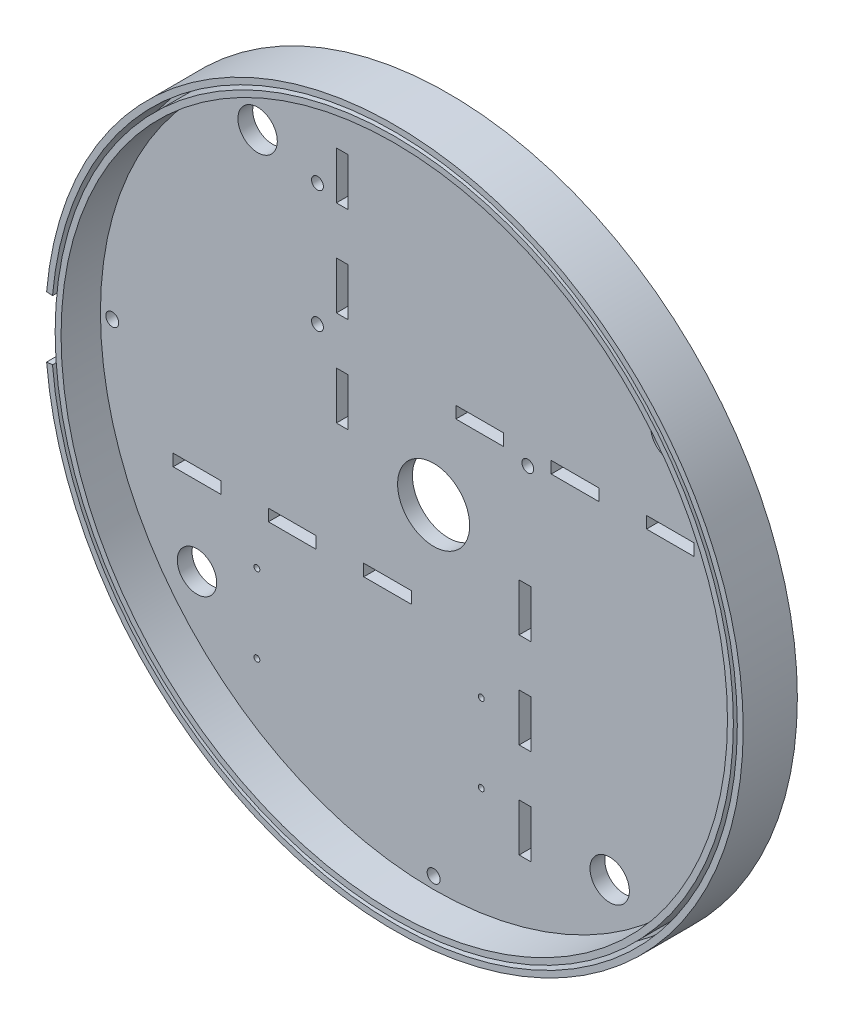
SolidWorks part; units mm, degrees
material "ABS"
ref_plane "Front Plane" through (0, 0, 0) normal (0, 0, 1) x (1, 0, 0)
ref_plane "Top Plane" through (0, 0, 0) normal (0, 1, 0) x (1, 0, 0)
ref_plane "Right Plane" through (0, 0, 0) normal (1, 0, 0) x (0, 0, -1)
sketch "Sketch1" plane through (0, 0, 0) normal (0, 0, 1) x (1, 0, 0)
  line L0 (0, 0) -> (0, -100) construction
  line L1 (-100, -100) -> (100, -100)
  line L2 (-100, -100) -> (-100, 100)
  line L3 (100, -100) -> (100, 100)
  line L4 (100, 100) -> (-100, 100)
  circle A0 centre (0, 0) radius 9.15
  point P7 (0, -100)
  dimension "D1" = 18.3
  dimension "D2" = 100
  dimension "D3" = 200
  dimension "D4" = 200
extrude "Boss-Extrude1" add sketch "Sketch1" against normal blind 3.75
sketch "Sketch2" plane through (0, 0, 0) normal (0, 0, 1) x (1, 0, 0)
  line L0 (0, 0) -> (0, 14.2) construction
  line L1 (0, 10.9) -> (0, 14.2)
  line L2 (8.825, 11.1247) -> (6.1526, 7.756)
  line L3 (-0.8481, 14.1747) -> (-0.5913, 9.8823)
  circle A0 centre (0, 0) radius 10.9 construction
  circle A1 centre (0, 0) radius 14.2
  circle A2 centre (0, 0) radius 10.9
  arc A3 (0, 12.55) -> (-0.7496, 12.5276) centre (0, 0) ccw construction
  arc A4 (0, 12.55) -> (0.7496, 12.5276) centre (0, 0) cw construction
  arc A5 (0.7496, 12.5276) -> (7.7995, 9.8321) centre (0, 0) cw construction
  arc A6 (0.8481, 14.1747) -> (8.825, 11.1247) centre (0, 0) cw
  arc A7 (0, 14.2) -> (0.8481, 14.1747) centre (0, 0) cw
  arc A8 (0, 14.2) -> (-0.8481, 14.1747) centre (0, 0) ccw
  arc A9 (0.5913, 9.8823) -> (6.1526, 7.756) centre (0, 0) cw
  arc A10 (0, 9.9) -> (0.5913, 9.8823) centre (0, 0) cw
  arc A11 (0, 9.9) -> (-0.5913, 9.8823) centre (0, 0) ccw
  dimension "D2" = 0.75
  dimension "D3" = 0.75
  dimension "D4" = 35
  dimension "D1" = 3.3
  dimension "D5" = 1.65
  dimension "D6" = 2.65
extrude "Cut-Extrude4" [suppressed] cut sketch "Sketch2" against normal mid plane 1.65 from offset 1.5 contours L2 A9 A10 A11 L3 A8 A7 A6 offset against normal yes
sketch "Sketch4" [suppressed] plane through (0, 0, -4.325) normal (0, 0, 1) x (1, 0, 0)
  line L0 (4.1191, 9.2766) -> (7.6444, 13.4263)
  line L1 (8.5363, 5.4912) -> (12.0972, 9.6104)
  arc A0 (6.6047, 7.7071) -> (8.5363, 5.4912) centre (0, 0) cw
  arc A1 (6.6047, 7.7071) -> (4.1191, 9.2766) centre (0, 0) ccw
  arc A2 (10.0535, 11.7316) -> (7.6444, 13.4263) centre (0, 0) ccw
  arc A3 (10.0535, 11.7316) -> (12.0972, 9.6104) centre (0, 0) cw
  dimension "D1" = 1.95
  dimension "D2" = 1.95
  dimension "D3" = 1.95
  dimension "D4" = 1.95
extrude "Cut-Extrude5" [suppressed] cut sketch "Sketch4" along normal through all
pattern_circular "CirPattern1" [suppressed] count 4 over 360 of bodies 108
sketch "Sketch5" plane through (0, 0, 0) normal (0, 0, 1) x (1, 0, 0)
  line L0 (0, 0) -> (15, 0)
  line L1 (15, 0) -> (47, 0)
  line L2 (47, 0) -> (15.5, 0)
  line L3 (15.5, 0) -> (5.65, 0)
  line L4 (5.65, 0) -> (5.65, 21.7)
  line L5 (5.65, 21.7) -> (17.75, 21.7)
  line L6 (5.65, 21.7) -> (5.65, 24.7)
  line L7 (17.75, 21.7) -> (17.75, 24.7)
  line L8 (5.65, 24.7) -> (17.75, 24.7)
  line L9 (17.75, 21.7) -> (29.85, 21.7)
  line L10 (29.85, 21.7) -> (29.85, 24.7)
  line L11 (29.85, 21.7) -> (41.95, 21.7)
  line L12 (29.85, 24.7) -> (41.95, 24.7)
  line L13 (41.95, 21.7) -> (41.95, 24.7)
  line L14 (41.95, 21.7) -> (54.05, 21.7)
  line L15 (54.05, 21.7) -> (66.15, 21.7)
  line L16 (54.05, 21.7) -> (54.05, 24.7)
  line L17 (66.15, 21.7) -> (66.15, 24.7)
  line L18 (54.05, 24.7) -> (66.15, 24.7)
  line L19 (60.1, 24.7) -> (60.1, 44.7) construction
  circle A0 centre (60.1, 44.7) radius 5
  point P22 (60.1, 24.7)
  dimension "D15" = 10
  dimension "D1" = 15
  dimension "D2" = 32
  dimension "D3" = 31.5
  dimension "D4" = 9.85
  dimension "D5" = 21.7
  dimension "D6" = 12.1
  dimension "D7" = 3
  dimension "D8" = 12.1
  dimension "D9" = 12.1
  dimension "D10" = 12.1
  dimension "D11" = 12.1
  dimension "D12" = 3
  dimension "D13" = 3
  dimension "D14" = 20
extrude "Cut-Extrude6" cut sketch "Sketch5" against normal blind 10 contours L11 L13 L12 L10 | L18 L16 L15 L17 | L5 L6 L8 L7 | A0 region at (60.1, 23.2, 0) region at (35.9, 23.2, 0)
pattern_circular "CirPattern2" count 4 over 360 about axis through (0, 0, -3.75) along (0, 0, 1) of "Cut-Extrude6"
sketch "Sketch6" plane through (0, 0, 0) normal (0, 0, 1) x (1, 0, 0)
  line L1 (100, 100) -> (-100, 100)
  line L2 (100, 100) -> (100, -100)
  line L3 (100, -100) -> (-100, -100)
  line L4 (-100, 100) -> (-100, -100)
  line L5 (100, 100) -> (-100, -100) construction
  line L6 (100, -100) -> (-100, 100) construction
  circle A0 centre (0, 0) radius 70.611 construction
  circle A1 centre (0, 0) radius 88.611
extrude "Cut-Extrude10" cut sketch "Sketch6" against normal through all contours L1 L4 L3 L2 A1 region at (97.1716, 0, 0)
sketch "Sketch7" plane through (0, 0, 0) normal (0, 0, 1) x (1, 0, 0)
  line L0 (-80.611, 0) -> (0, 0) construction
  line L1 (-88.2738, 7.723) -> (-86.7795, 7.5922)
  line L2 (-88.2738, -7.723) -> (-86.7795, -7.5922)
  circle A0 centre (0, 0) radius 88.611 construction
  arc A1 (-88.2738, -7.723) -> (-88.2738, 7.723) centre (0, 0) cw construction
  arc A2 (-88.2738, 7.723) -> (-88.2738, -7.723) centre (0, 0) cw
  arc A3 (-86.7795, 7.5922) -> (-86.7795, -7.5922) centre (0, 0) cw
  circle A4 centre (0, 0) radius 86.111
  circle A5 centre (0, 0) radius 84.611
  circle A6 centre (0, 0) radius 88.611 construction
  dimension "D1" = 1.5
  dimension "D2" = 2.5
  dimension "D3" = 1.5
extrude "Boss-Extrude2" add sketch "Sketch7" along normal blind 10
sketch "Sketch8" plane through (0, 0, -3.75) normal (0, 0, -1) x (-1, 0, 0)
  line L0 (0, 0) -> (-88.611, 0) construction
  line L1 (0, 0) -> (-83.2671, -30.3067) construction
  circle A0 centre (0, 0) radius 88.611 construction
  dimension "D1" = 20
ref_plane "Plane1" through (83.2671, 0, 0) normal (1, 0, 0) x (0, 0, -1)
sketch "Sketch9" plane through (83.2671, 0, 0) normal (1, 0, 0) x (0, 0, -1)
  line L0 (3.75, -30.3067) -> (0, -30.3067) construction
  circle A0 centre (1.875, -30.3067) radius 0.75
  dimension "D1" = 3.75
  dimension "D2" = 1.5
sketch "Sketch10" plane through (0, 0, -3.75) normal (0, 0, -1) x (-1, 0, 0)
  point P0 (29.5, 56)
  point P1 (29.5, 25)
  point P2 (-23.9, 20.5)
  point P3 (-23.9, 70.5)
  point P4 (44.8862, -36.3499)
  point P5 (44.8862, -56.2286)
  point P7 (-12.0925, -56.2286)
  point P9 (-12.0925, -36.3499)
  dimension "D1" = 31
  dimension "D2" = 50
  dimension "D3" = 53.4
  dimension "D4" = 19.8787
  dimension "D5" = 56.9787
  dimension "D6" = 19.8787
  dimension "D7" = 25
  dimension "D8" = 29.5
  dimension "D9" = 20.5
sketch "Sketch11" plane through (0, 0, -3.75) normal (0, 0, -1) x (-1, 0, 0)
  line L0 (29.5, 56) -> (29.5, 25) construction
  line L1 (-23.9, 70.5) -> (-23.9, 20.5) construction
  line L2 (-26.4, 70.5) -> (-26.4, 20.5)
  line L3 (-21.4, 70.5) -> (-21.4, 20.5)
  line L10 (27, 56) -> (27, 25)
  line L11 (32, 56) -> (32, 25)
  circle A0 centre (29.5, 25) radius 1.5
  circle A1 centre (29.5, 56) radius 1.5
  circle A2 centre (-23.9, 70.5) radius 1.5
  circle A3 centre (-23.9, 20.5) radius 1.5
  arc A4 (27, 56) -> (32, 56) centre (29.5, 56) cw
  arc A5 (27, 25) -> (32, 25) centre (29.5, 25) ccw
  arc A6 (-26.4, 70.5) -> (-21.4, 70.5) centre (-23.9, 70.5) cw
  arc A7 (-26.4, 20.5) -> (-21.4, 20.5) centre (-23.9, 20.5) ccw
  dimension "D13" = 3
  dimension "D14" = 3
  dimension "D15" = 3
  dimension "D16" = 3
  dimension "D2" = 2.5
  dimension "D3" = 2.5
  dimension "D7" = 2.5
  dimension "D8" = 2.5
extrude "Boss-Extrude3" add sketch "Sketch11" along normal blind 5
sketch "Sketch13" plane through (0, 0, -3.75) normal (0, 0, -1) x (-1, 0, 0)
  circle A0 centre (29.5, 56) radius 1.5
  circle A1 centre (29.5, 25) radius 1.5
  circle A2 centre (-23.9, 20.5) radius 1.5
  circle A3 centre (-23.9, 70.5) radius 1.5
extrude "Cut-Extrude11" cut sketch "Sketch13" against normal through all
sketch "Sketch14" plane through (0, 0, -3.75) normal (0, 0, -1) x (-1, 0, 0)
  line L0 (44.8862, -36.3499) -> (44.8862, -56.2286)
  line L1 (-12.0925, -36.3499) -> (-12.0925, -56.2286)
  line L2 (-9.5925, -36.3499) -> (-9.5925, -56.2286)
  line L3 (-14.5925, -36.3499) -> (-14.5925, -56.2286)
  line L4 (42.3862, -36.3499) -> (42.3862, -56.2286)
  line L5 (47.3862, -36.3499) -> (47.3862, -56.2286)
  arc A0 (-9.5925, -36.3499) -> (-14.5925, -36.3499) centre (-12.0925, -36.3499) ccw
  arc A1 (-9.5925, -56.2286) -> (-14.5925, -56.2286) centre (-12.0925, -56.2286) cw
  arc A2 (42.3862, -36.3499) -> (47.3862, -36.3499) centre (44.8862, -36.3499) cw
  arc A3 (42.3862, -56.2286) -> (47.3862, -56.2286) centre (44.8862, -56.2286) ccw
  circle A4 centre (44.8862, -36.3499) radius 0.75
  circle A6 centre (-12.0925, -56.2286) radius 0.75
  circle A7 centre (-12.0925, -36.3499) radius 0.75
  circle A8 centre (44.8862, -56.2286) radius 0.75
  dimension "D5" = 1.5
  dimension "D6" = 1.5
  dimension "D7" = 1.5
  dimension "D8" = 1.5
  dimension "D1" = 2.5
  dimension "D2" = 2.5
  dimension "D3" = 2.5
  dimension "D4" = 2.5
extrude "Boss-Extrude4" add sketch "Sketch14" along normal blind 3 contours L4 A3 L5 A2 A8 A4 | A1 L2 A0 L3 A7 A6 region at (9.8462, -46.2892, -3.75) region at (-44.8862, -34.1037, -3.75)
extrude "Cut-Extrude12" cut sketch "Sketch14<3>" against normal through all contours A4 | A8 | A6 | A7
sketch "Sketch14<3>" plane through (0, 0, -3.75) normal (0, 0, -1) x (-1, 0, 0) same geometry as "Sketch14"
sketch "Sketch15" plane through (0, 0, 0) normal (0, 0, 1) x (1, 0, 0)
  line L0 (0, 0) -> (-86.111, 0) construction
  line L1 (-86.111, 0) -> (-81.611, 0)
  circle A0 centre (0, 0) radius 86.111 construction
  dimension "D1" = 4.5
hole_wizard "Tap Drill for M4x0.7 Tap1" positions "Sketch20" profile "Sketch22" hole size "M4x0.7" standard "BSI" end condition through all
sketch "Sketch20" plane through (0, 0, 0) normal (0, 0, 1) x (1, 0, 0)
  point P0 (-81.611, 0)
sketch "Sketch22" plane through (-81.611, 0, 0) normal (1, 0, 0) x (0, -1, 0)
  line L0 (0, 0) -> (0, 8.75)
  line L1 (0, 8.75) -> (1.65, 8.75)
  line L2 (1.65, 8.75) -> (1.65, 0)
  line L5 (1.65, 0) -> (0, 0)
  line L11 (0, -6.35) -> (0, 107.95) construction
  dimension "Thru Hole Dia." = 3.3
  dimension "Thru Hole Depth" = 8.75
pattern_circular "CirPattern3" count 4 over 360 about axis through (0, 0, 10) along (0, 0, 1) of "Tap Drill for M4x0.7 Tap1"
equation "\"OuterThickness\"= 3mm"
equation "\"MasterFillet\"= 3mm"
equation "\"PartSeperation\"= 6mm"
equation "\"Tolerance\"= 0.15mm"
equation "\"HeightPart\"= 100mm"
equation "\"Holes\"= 1.5mm"
equation "\"SpineHolderThickness\"= 3mm"
equation "\"SpineHolderDepth\" = 3mm"
equation "\"D1@Sketch1\"= \"SpineDiameter\" + \"SpineHolderThickness\" + \"Tolerance\" * 2"
equation "\"D3@Sketch1\"=\"HeightPart\"*2"
equation "\"D4@Sketch1\"=\"HeightPart\"*2"
equation "\"D1@Boss-Extrude1\"=\"SpineHolderDepth\"*1.25"
equation "\"D1@Sketch2\"=\"Tolerance\"*2+\"SpineHolderThickness\""
equation "\"D2@Sketch2\"=\"SpineHolderThickness\"/4"
equation "\"D3@Sketch2\"=\"SpineHolderThickness\"/4"
equation "\"D5@Sketch2\"=\"Tolerance\"+\"SpineHolderThickness\"/2"
equation "\"D19@Cut-Extrude4\"=\"SpineHolderDepth\"/2"
equation "\"D1@Cut-Extrude4\"=\"SpineHolderThickness\"/2+\"Tolerance\""
equation "\"D1@Sketch4\"=\"Tolerance\"*3+\"SpineHolderThickness\"/2"
equation "\"D2@Sketch4\"=\"Tolerance\"*3+\"SpineHolderThickness\"/2"
equation "\"D3@Sketch4\"=\"Tolerance\"*3+\"SpineHolderThickness\"/2"
equation "\"D4@Sketch4\"=\"Tolerance\"*3+\"SpineHolderThickness\"/2"
equation "\"D2@Sketch1\"=\"HeightPart\""
equation "\"MotorLength\" = 40.5mm"
equation "\"MotorWidth\" = 20.3mm"
equation "\"AttachmentHeight\"= 3mm"
equation "\"SpoolDiameter\"= 60mm"
equation "\"SpoolHeight\"= 2mm"
equation "\"SpoolRidgeHeight\"= 1mm"
equation "\"SpoolRidgeDepth\"= 2mm"
equation "\"SpoolSeperation\"= 2mm"
equation "\"ServoHolderWidthOffset\"= 20mm"
equation "\"MotorTransmitterToScrew\"= 21.7mm"
equation "\"SpoolToSpine\"= 15mm"
equation "\"D1@Sketch5\"=\"SpoolToSpine\""
equation "\"D2@Sketch5\"=\"SpoolDiameter\"/2+\"SpoolRidgeDepth\""
equation "\"SpoolCenterToMotor\" = 31.5mm"
equation "\"D3@Sketch5\"=\"SpoolCenterToMotor\""
equation "\"D4@Sketch5\"=((\"MotorLength\"+\"ServoHolderWidthOffset\")-(\"MotorLength\"+\"Tolerance\"*2))/2"
equation "\"D5@Sketch5\"=\"MotorTransmitterToScrew\""
equation "\"D6@Sketch5\"=(\"MotorLength\"+\"ServoHolderWidthOffset\")*1/5"
equation "\"D7@Sketch5\"=3"
equation "\"D8@Sketch5\"=(\"MotorLength\"+\"ServoHolderWidthOffset\")*1/5"
equation "\"D9@Sketch5\"=(\"MotorLength\"+\"ServoHolderWidthOffset\")*1/5"
equation "\"D10@Sketch5\"=(\"MotorLength\"+\"ServoHolderWidthOffset\")*1/5"
equation "\"D11@Sketch5\"=(\"MotorLength\"+\"ServoHolderWidthOffset\")*1/5"
equation "\"D12@Sketch5\"=3"
equation "\"D13@Sketch5\"=3"
equation "\"HubOffset\"= 18mm"
equation "\"D1@Sketch6\"=\"HubOffset\""
equation "\"D1@Sketch9\"=\"SpineHolderDepth\"*1.25"
equation "\"D2@Sketch9\"=\"SpineHolderDepth\"/2"
equation "\"ArduinoLength\" = 53.4mm"
equation "\"D3@Sketch10\"=\"ArduinoLength\""
equation "\"ArduinoWidth\" = 50mm"
equation "\"D2@Sketch10\"=\"ArduinoWidth\""
equation "\"ArdYOffset\" = 29.5mm"
equation "\"D8@Sketch10\"=\"ArdYOffset\""
equation "\"ArdXOffset\" = 20.5mm"
equation "\"D9@Sketch10\"=\"ArdXOffset\""
equation "\"ArdXOffsetSmall\" = 25mm"
equation "\"D7@Sketch10\"=\"ArdXOffsetSmall\""
equation "\"DiscThickness\"= 4mm"
equation "\"LigamentThickness\"= 2mm"
equation "\"LigamentExtension\"= 1mm"
equation "\"LigamentAngle\"= 20deg"
equation "\"SpineDiameter\"= 15mm"
equation "\"LigamentDepth\"= 1mm"
equation "\"ServoFastenerHolders\"=2mm"
equation "\"MiddleServoOffset\"= 12mm"
equation "\"LargeServoOffset\"= 3mm"
equation "\"SmallServoOffset\"= 0mm"
equation "\"ToolHoleDiameter\"= 12mm"
equation "\"PartThickness\"= 4mm"
equation "\"TendonThickness\"= 2mm"
